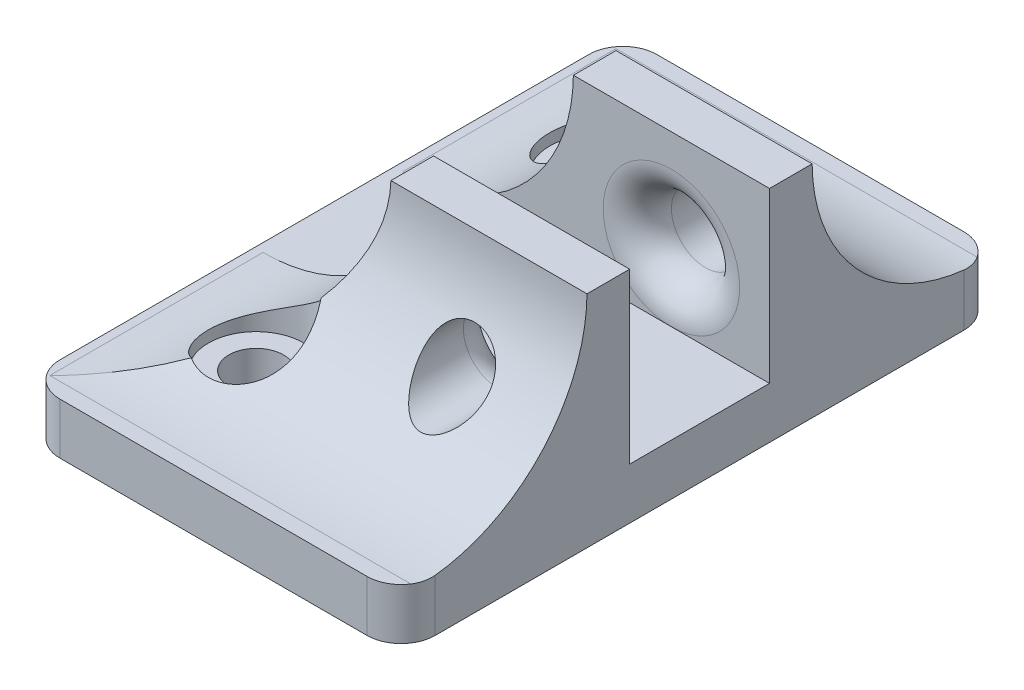
SolidWorks part; units mm, degrees
ref_plane "Alzado" through (0, 0, 0) normal (0, 0, 1) x (1, 0, 0)
ref_plane "Planta" through (0, 0, 0) normal (0, 1, 0) x (1, 0, 0)
ref_plane "Vista lateral" through (0, 0, 0) normal (1, 0, 0) x (0, 0, -1)
sketch "Croquis1" plane through (0, 0, 0) normal (0, 1, 0) x (1, 0, 0)
  line L1 (0, 0) -> (22, 0)
  line L2 (0, 0) -> (0, 35)
  line L3 (0, 35) -> (22, 35)
  line L4 (22, 0) -> (22, 35)
  circle A0 centre (6, 27.5) radius 1.6
  circle A1 centre (6, 7.5) radius 1.6
  point P9 (0, 0)
  point P10 (0, 0)
  dimension "D2" = 3.2
  dimension "D1" = 35
  dimension "D3" = 20
  dimension "D4" = 7.5
  dimension "D5" = 6
  dimension "D6" = 22
extrude "Saliente-Extruir1" add sketch "Croquis1" along normal blind 3
sketch "Croquis2" plane through (0, 3, 0) normal (0, 1, 0) x (1, 0, 0)
  line L0 (22, 0) -> (22, 35) construction
  line L1 (22, 24.1) -> (10.5, 24.1)
  line L2 (22, 24.1) -> (22, 10.9)
  line L3 (22, 10.9) -> (10.5, 10.9)
  line L4 (10.5, 24.1) -> (10.5, 21.6)
  line L5 (10.5, 21.6) -> (22, 21.6)
  line L6 (10.5, 13.4) -> (22, 13.4)
  line L7 (10.5, 13.4) -> (10.5, 10.9)
  line L8 (22, 35) -> (0, 35) construction
  line M9 (22, 0) -> (22, 35)
  dimension "D1" = 13.2
  dimension "D2" = 2.5
  dimension "D3" = 2.5
  dimension "D4" = 10.9
  dimension "D5" = 11.5
extrude "Saliente-Extruir2" add sketch "Croquis2" along normal blind 9.9 contours L4 L5 L2 L1 | L6 L7 L3 M9 region at (16.25, 3, -22.85) region at (16.25, 3, -12.15)
sketch "Croquis4" plane through (0, 0, -21.6) normal (0, 0, 1) x (1, 0, 0)
  line L0 (10.5, 12.9) -> (10.5, 3) construction
  line L1 (10.5, 3) -> (22, 3) construction
  circle A0 centre (16.25, 7) radius 2
  point P4 (0, 0)
  dimension "D1" = 4
  dimension "D2" = 5.75
  dimension "D3" = 4
extrude "Cortar-Extruir1" cut sketch "Croquis4" against normal up to surface (2.5 mm away) up to face at (16.25, 7.95, -24.1)
sketch "Croquis5" plane through (0, 0, -13.4) normal (0, 0, -1) x (-1, 0, 0)
  circle A0 centre (-16.25, 7) radius 2 construction
  circle A1 centre (-16.25, 7) radius 2
extrude "Cortar-Extruir2" cut sketch "Croquis5" against normal up to surface (2.5 mm away) up to face at (16.25, 7.95, -10.9)
sketch "Croquis6" plane through (0, 3, 0) normal (0, 1, 0) x (1, 0, 0)
  circle A0 centre (6, 7.5) radius 2.8
  circle A1 centre (6, 27.5) radius 2.8
  dimension "D1" = 5.6
extrude "Cortar-Extruir3" cut sketch "Croquis6" against normal blind 0.3
fillet "Redondeo1" radius 2 2 edges at (14.25, 7, -13.4) (18.25, 7, -21.6)
fillet "Redondeo2" radius 10 4 edges at (16.25, 3, -24.1) (10.5, 3, -22.85) (10.5, 3, -12.15) (16.25, 3, -10.9)
fillet "Redondeo4" radius 2 4 edges at (0, 1.5, -35) (0, 1.5, 0) (22, 1.5, 0) (22, 1.5, -35)
